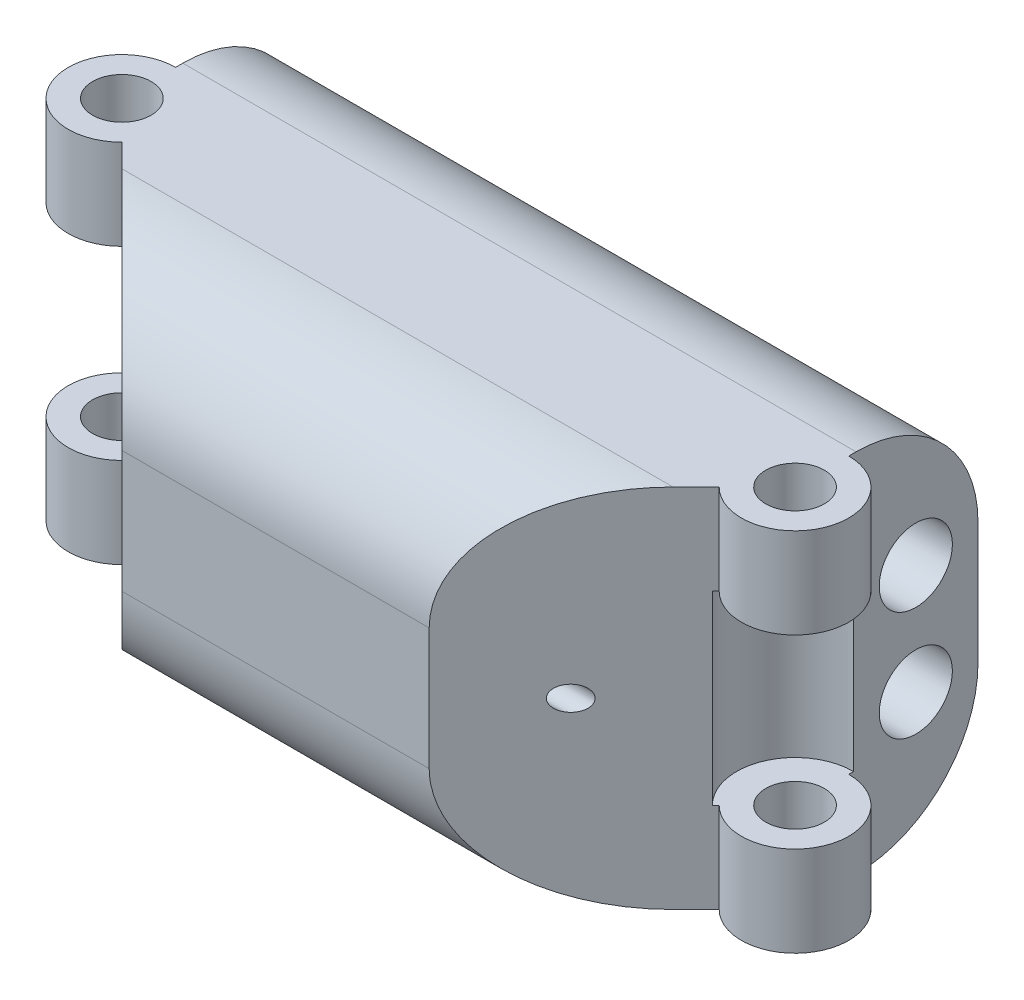
SolidWorks part; units mm, degrees
ref_plane "Front Plane" through (0, 0, 0) normal (1, 0, 0) x (0, 1, 0)
ref_plane "Top Plane" through (0, 0, 0) normal (0, 0, 1) x (0, 1, 0)
ref_plane "Right Plane" through (0, 0, 0) normal (0, 1, 0) x (-1, 0, 0)
sketch "Sketch1" plane through (0, 0, 0) normal (0, 1, 0) x (-1, 0, 0)
  line L1 (-6.3, 7.5) -> (6.3, 7.5)
  line L4 (13.8, -7.5) -> (-13.8, -7.5)
  line L6 (-13.8, -7.5) -> (-13.8, 0)
  line L7 (-13.8, 7.5) -> (-6.3, 7.5) construction
  line L8 (6.3, 7.5) -> (13.8, 7.5) construction
  line L9 (6.3, 7.5) -> (13.8, 0)
  line L10 (-13.8, 7.5) -> (13.8, -7.5) construction
  line L11 (-13.8, 0) -> (-6.3, 7.5)
  line L12 (-13.8, 7.5) -> (-13.8, 0) construction
  line L13 (13.8, 0) -> (13.8, -7.5)
  line L14 (13.8, 0) -> (13.8, 7.5) construction
  arc A4 (12.1029, 1.6971) -> (13.8, -2.4) centre (13.8, 0) ccw
  circle A5 centre (13.8, 0) radius 1.2 construction
  circle A6 centre (13.8, 0) radius 2.2 construction
  arc A7 (-13.8, -2.4) -> (-12.1029, 1.6971) centre (-13.8, 0) ccw
  dimension "D3" = 1
  dimension "D4" = 0.2
  dimension "D5" = 4.8
  dimension "D2" = 2.4
  dimension "D1" = 15
extrude "Boss-Extrude1" add sketch "Sketch1" along normal blind 7.5 and the other way blind 7.5 contours L1 L4 region at (0, 0, -0.7982)
sketch "Sketch5" plane through (13.8, 0, 0) normal (1, 0, 0) x (0, 1, 0)
  line L0 (0, -2.4) -> (0, -7.5) construction
  line L1 (-2.25, -4.95) -> (2.25, -4.95) construction
  line L2 (-7.5, -2.4) -> (7.5, -2.4) construction
  line L3 (-7.5, -7.5) -> (7.5, -7.5) construction
  circle A0 centre (-2.25, -4.95) radius 1.5
  circle A1 centre (2.25, -4.95) radius 1.5
  point P4 (0.75, -4.95)
  point P7 (0, -4.95)
  point P8 (-0.75, -4.95)
  point P9 (0, -4.95)
  dimension "D1" = 3
  dimension "D2" = 1.5
  dimension "D3" = 0
extrude "Cut-Extrude3" cut sketch "Sketch5" against normal up to next
fillet "Fillet1" radius 5 2 edges at (0, -7.5, -7.5) (0, 7.5, -7.5)
sketch "Sketch3" plane through (0, 0, 0) normal (1, 0, 0) x (0, 1, 0)
  line L0 (-7.5, 4.5985) -> (7.5, 4.5985) construction
  line L3 (-7.5, 1.6971) -> (-7.5, 7.5) construction
  line L4 (7.5, 1.6971) -> (7.5, 7.5) construction
  circle A0 centre (0, 4.5985) radius 0.5
extrude "Cut-Extrude2" cut sketch "Sketch3" against normal up to next and the other way up to next
fillet "Fillet2" radius 5 2 edges at (0, 7.5, 7.5) (0, -7.5, 7.5)
sketch "Sketch6" plane through (0, 0, 0) normal (0, 1, 0) x (-1, 0, 0)
  line L4 (0, 7.5) -> (0, -7.5) construction
  line L5 (-6.3, 7.5) -> (6.3, 7.5) construction
  line L6 (13.8, -7.5) -> (-13.8, -7.5) construction
  line L7 (-12.1029, 1.6971) -> (-12.2444, 1.5556)
  line L9 (-13.8, -2.4) -> (-13.8, -2.2)
  line L10 (-12.1029, 1.6971) -> (-11.3, 2.5) construction
  line L11 (13.8, -2.4) -> (13.8, -2.2)
  line L12 (12.1029, 1.6971) -> (12.2444, 1.5556)
  arc A6 (-12.2444, 1.5556) -> (-13.8, -2.2) centre (-13.8, 0) ccw
  circle A7 centre (-13.8, 0) radius 1.2
  arc A8 (-13.8, -2.4) -> (-12.1029, 1.6971) centre (-13.8, 0) ccw
  arc A9 (-13.8, -2.4) -> (-12.1029, 1.6971) centre (-13.8, 0) ccw construction
  arc A10 (13.8, -2.4) -> (12.1029, 1.6971) centre (13.8, 0) cw
  circle A11 centre (13.8, 0) radius 1.2
  arc A12 (12.2444, 1.5556) -> (13.8, -2.2) centre (13.8, 0) cw
  dimension "D1" = 0.2
  dimension "D2" = 1
extrude "Boss-Extrude2" add sketch "Sketch6" along normal blind 3.7 from offset 3.8
extrude "Boss-Extrude3" add sketch "Sketch6<4>" against normal blind 3.7 from offset 3.8 offset against normal yes
sketch "Sketch6<4>" plane through (0, 0, 0) normal (0, 1, 0) x (-1, 0, 0) same geometry as "Sketch6"
